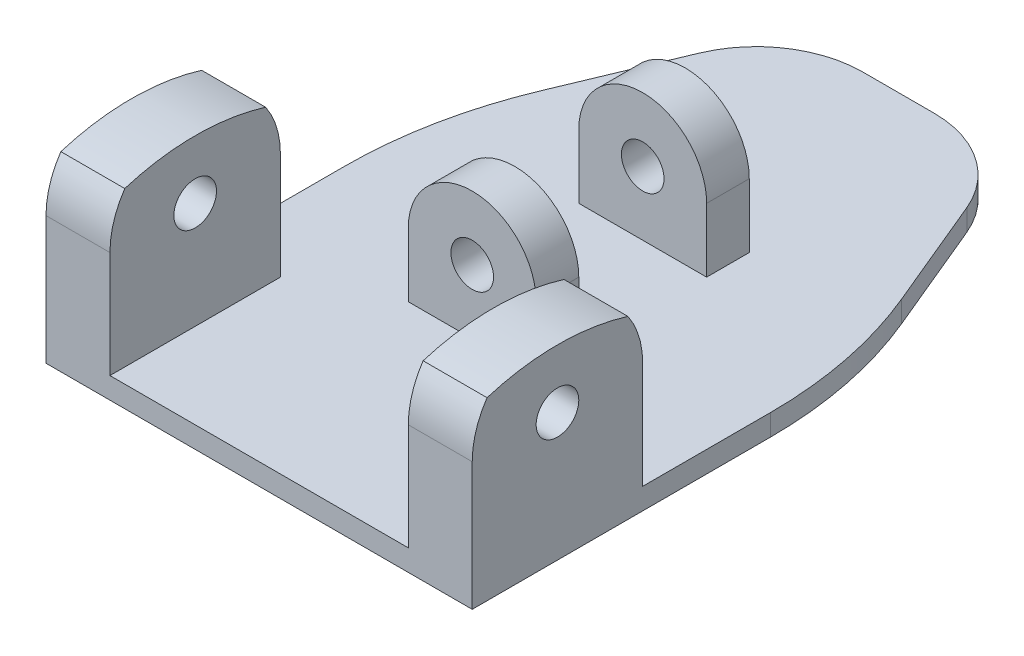
SolidWorks part; units mm, degrees
ref_plane "前视基准面" through (0, 0, 0) normal (0, 0, 1) x (1, 0, 0)
ref_plane "上视基准面" through (0, 0, 0) normal (0, 1, 0) x (1, 0, 0)
ref_plane "右视基准面" through (0, 0, 0) normal (1, 0, 0) x (0, 0, -1)
other "Configuration Table"
sketch "草图1" plane through (0, 0, 0) normal (0, 1, 0) x (1, 0, 0)
  line L0 (0, 0) -> (0, 255.8207) construction
  line L1 (-100, 0) -> (100, 0)
  line L2 (100, 0) -> (100, 180)
  line L3 (100, 180) -> (50, 300)
  line L4 (50, 300) -> (-50, 300)
  line L5 (-100, 180) -> (-50, 300)
  line L6 (-100, 0) -> (-100, 180)
  point P8 (0, 300)
  dimension "D1" = 300
  dimension "D2" = 100
  dimension "D3" = 120
  dimension "D4" = 50
extrude "凸台-拉伸1" add sketch "草图1" along normal blind 10
sketch "草图2" plane through (100, 0, 0) normal (1, 0, 0) x (0, 0, -1)
  line L0 (40, 100) -> (40, -10.3339) construction
  line L1 (0, 10) -> (0, 0) construction
  line L2 (0, 10) -> (0, 60)
  line L3 (80, 10) -> (80, 60)
  arc A0 (80, 60) -> (0, 60) centre (40, 60) ccw
  circle A1 centre (40, 60) radius 10
  line M6 (180, 10) -> (0, 10)
  dimension "D3" = 20
  dimension "D1" = 40
  dimension "D2" = 50
extrude "凸台-拉伸2" add sketch "草图2" against normal up to surface (200 mm away) contours A0 L0 A1 L3 M6 | L0 A0 L2 A1 M6 region at (100, 50.7514, -59.5727) region at (100, 50.7514, -20.4273) up to face at (-100, 5, -90)
sketch "草图3" plane through (0, 10, 0) normal (0, 1, 0) x (1, 0, 0)
  line L0 (0, 0) -> (0, 135.8056) construction
  line L1 (-100, 0) -> (100, 0) construction
  line L2 (-70, 0) -> (70, 0)
  line L3 (-70, 0) -> (-70, 100)
  line L4 (-70, 100) -> (70, 100)
  line L5 (70, 0) -> (70, 100)
  line L6 (100, 0) -> (100, 80) construction
  line L7 (-100, 80) -> (-100, 0) construction
  dimension "D1" = 30
  dimension "D2" = 30
  dimension "D3" = 100
extrude "切除-拉伸1" cut sketch "草图3" along normal blind 171
sketch "草图4" plane through (0, 0, 0) normal (0, 0, 1) x (1, 0, 0)
  line L0 (0, 0) -> (0, 92.3322) construction
  line L1 (30, 40) -> (30, 10)
  line L2 (-30, 40) -> (-30, 10)
  line L3 (-70, 10) -> (70, 10) construction
  arc A0 (-30, 40) -> (30, 40) centre (0, 40) cw
  circle A1 centre (0, 40) radius 10
  line M10 (70, 10) -> (-70, 10)
  dimension "D2" = 30
  dimension "D3" = 20
  dimension "D1" = 30
extrude "凸台-拉伸3" add sketch "草图4" against normal blind 100 from offset 100 contours L0 L1 A0 A1 M10 | L0 A1 A0 L2 M10 region at (-15.0598, 36.8961, 0) region at (15.0598, 36.8961, 0) offset against normal yes
sketch "草图5" plane through (0, 10, 0) normal (0, 1, 0) x (1, 0, 0)
  line L0 (-47.074, 150) -> (51.1394, 150) construction
  line L1 (30, 200) -> (-30, 200) construction
  line L2 (30, 100) -> (-30, 100) construction
  line L3 (-30, 100) -> (30, 100) construction
  line L4 (-40, 180) -> (40, 180)
  line L5 (-40, 180) -> (-40, 120)
  line L6 (-40, 120) -> (40, 120)
  line L7 (40, 180) -> (40, 120)
  line L8 (30, 200) -> (30, 100) construction
  line L9 (-30, 200) -> (-30, 100) construction
  dimension "D1" = 20
  dimension "D2" = 20
  dimension "D3" = 10
  dimension "D4" = 10
extrude "切除-拉伸2" cut sketch "草图5" along normal blind 110 contours L7 L6 L5 L4
fillet "圆角1" radius 50 2 edges at (-50, 5, -300) (50, 5, -300)
fillet "圆角2" radius 200 2 edges at (-100, 5, -180) (100, 5, -180)
sketch "草图6" plane through (100, 0, 0) normal (1, 0, 0) x (0, 0, -1)
  line L0 (40, 60) -> (40, -52.2503) construction
  circle A0 centre (40, 60) radius 10 construction
  circle A1 centre (40, 60) radius 10 construction
  arc A2 (73.0468, 82.5368) -> (6.9532, 82.5368) centre (40, -25) ccw
  arc A3 (80, 60) -> (0, 60) centre (40, 60) ccw construction
  arc A4 (73.0468, 82.5368) -> (6.9532, 82.5368) centre (40, 60) ccw
  dimension "D2" = 225
  dimension "D1" = 25
extrude "切除-拉伸3" cut sketch "草图6" against normal through all both and the other way through all contours A2 A4
